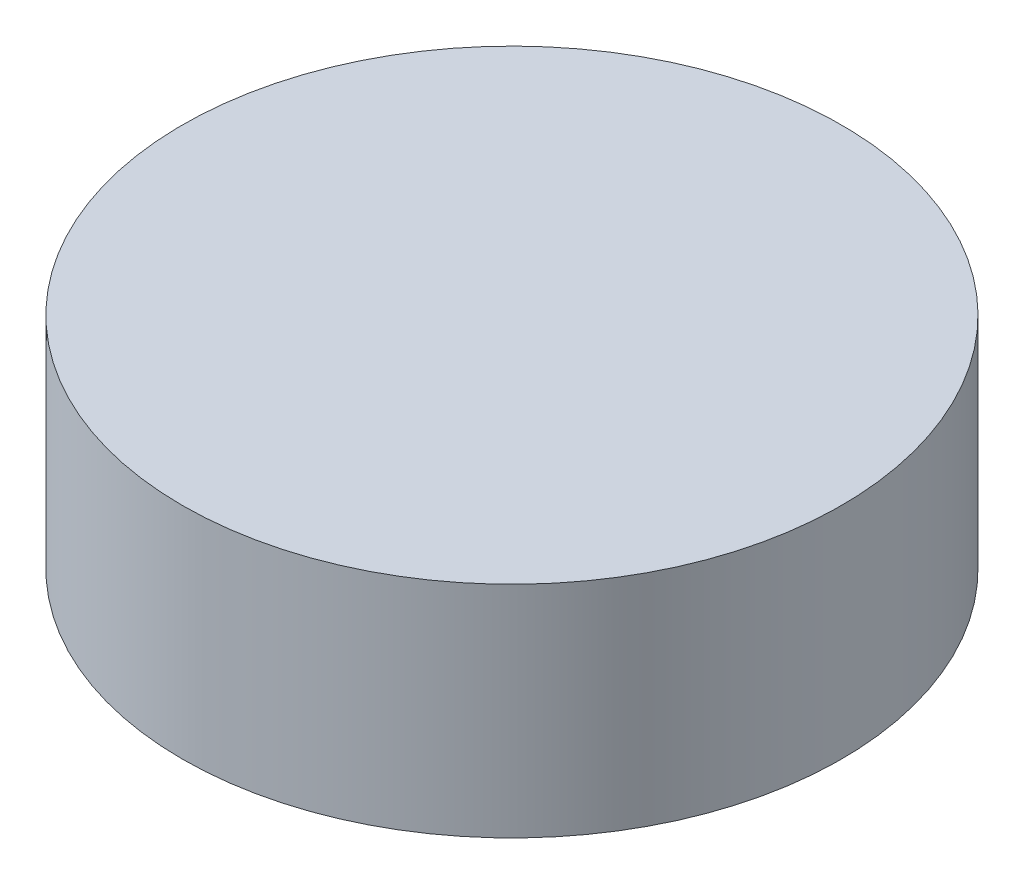
SolidWorks part; units mm, degrees
ref_plane "Front Plane" through (0, 0, 0) normal (0, 0, 1) x (1, 0, 0)
ref_plane "Top Plane" through (0, 0, 0) normal (0, 1, 0) x (1, 0, 0)
ref_plane "Right Plane" through (0, 0, 0) normal (1, 0, 0) x (0, 0, -1)
sketch "Sketch1" plane through (0, 0, 0) normal (0, 1, 0) x (1, 0, 0)
  circle A0 centre (0, 0) radius 38.1
  dimension "D1" = 76.2
extrude "Boss-Extrude1" add sketch "Sketch1" along normal blind 25.4
ref_axis "Axis1" through (0, -1.27, 0) along (0, 1, 0)
